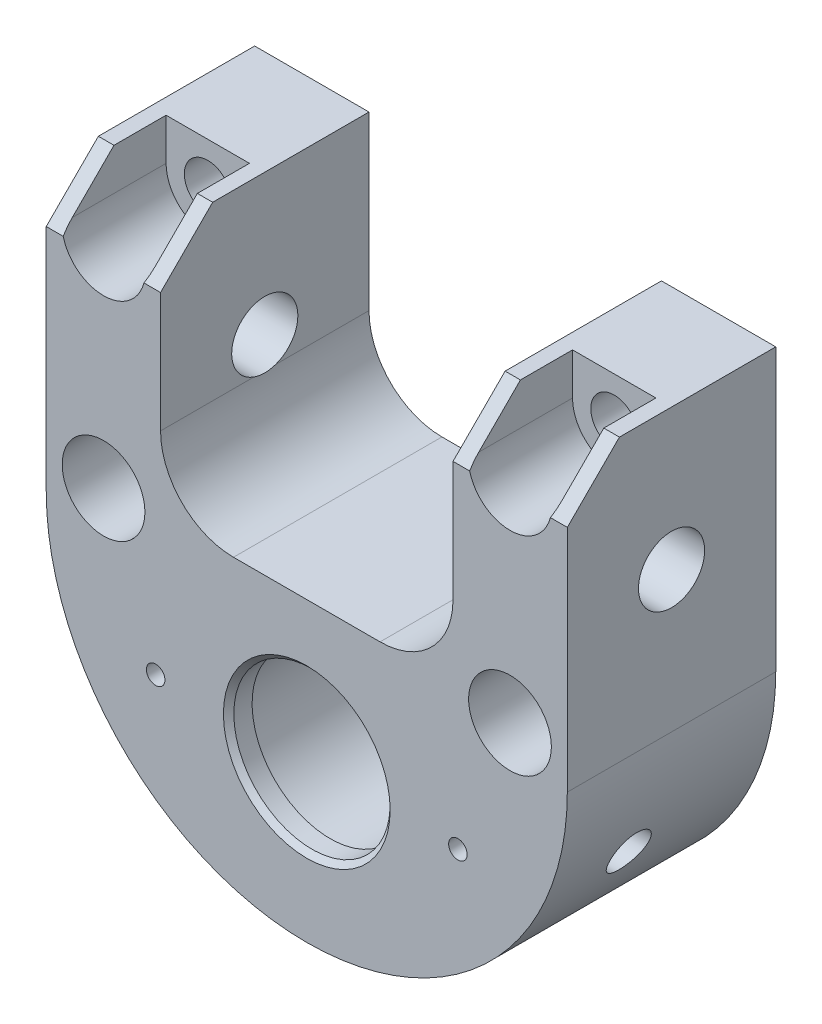
SolidWorks part; units mm, degrees
material "AISI 316 Annealed Stainless Steel Bar (SS)"
ref_plane "Front" through (0, 0, 0) normal (0, 0, 1) x (1, 0, 0)
ref_plane "Top" through (0, 0, 0) normal (0, 1, 0) x (1, 0, 0)
ref_plane "Right" through (0, 0, 0) normal (1, 0, 0) x (0, 0, -1)
sketch "Sketch1" plane through (0, 0, 0) normal (0, 0, 1) x (1, 0, 0)
  line L0 (0, 37) -> (0, 0) construction
  line L1 (-25, -15) -> (25, -15)
  line L2 (-25, -15) -> (-25, 37)
  line L3 (-25, 37) -> (25, 37)
  line L4 (25, -15) -> (25, 37)
  circle A0 centre (0, 0) radius 9.5 construction
  dimension "D3" = 19
  dimension "D5" = 15
  dimension "D1" = 52
  dimension "D2" = 50
extrude "Boss-Extrude1" add sketch "Sketch1" along normal blind 20
sketch "Sketch3" plane through (0, 0, 0) normal (1, 0, 0) x (0, 0, -1)
  line L0 (0, 0) -> (-20, 0)
  line L1 (-20, 0) -> (-20, 7.5)
  line L2 (-20, 7.5) -> (-17.75, 7.5)
  line L3 (-17.75, 7.5) -> (-17.75, 8)
  line L4 (-17.75, 8) -> (-7, 8)
  line L5 (-7, 8) -> (-7, 11)
  line L6 (-7, 11) -> (0, 11)
  line L7 (0, 37) -> (0, 0) construction
  line L8 (0, 11) -> (0, 0)
  line L9 (-20, -15) -> (-20, 37) construction
  dimension "D1" = 11
  dimension "D2" = 8
  dimension "D3" = 7.5
  dimension "D4" = 7
  dimension "D5" = 2.25
revolve "Cut-Revolve1" cut sketch "Sketch3" angle 360 about L0
hole_wizard "5/32 (0.15625) Diameter Hole1" positions "Sketch4" profile "Sketch5" hole size "5/32" standard "ANSI Inch" end condition up to next
sketch "Sketch4" plane through (25, 0, 0) normal (1, 0, 0) x (0, 0, -1)
  line L1 (0, 0) -> (-20, 0) construction
  line L2 (-20, -15) -> (-20, 37) construction
  point P0 (-12, 0)
  dimension "D1" = 8
sketch "Sketch5" plane through (25, 0, 12) normal (0, 1, 0) x (0, 0, -1)
  line L0 (0, 0) -> (0, 17)
  line L1 (0, 17) -> (1.9844, 17)
  line L2 (1.9844, 17) -> (1.9844, 0)
  line L5 (1.9844, 0) -> (0, 0)
  line L11 (0, -6.35) -> (0, 107.95) construction
  dimension "Thru Hole Dia." = 3.9688
  dimension "Thru Hole Depth" = 17
fillet "Fillet1" radius 5 1 edges at (0, 37, 20) profile chamfer
hole_wizard "#2-56 Tapped Hole1" positions "Sketch8" profile "Sketch9" tap size "#2-56" standard "ANSI Inch"
sketch "Sketch8" plane through (0, 0, 20) normal (0, 0, 1) x (1, 0, 0)
  line L0 (-14.5, 0) -> (14.5, 0)
  point P0 (-14.5, 0)
  point P2 (14.5, 0)
  dimension "D1" = 29
sketch "Sketch9" plane through (-14.5, 0, 20) normal (1, 0, 0) x (0, -1, 0)
  line L0 (0, 0) -> (0, 8.4542)
  line L1 (0, 8.4542) -> (0.889, 7.92)
  line L2 (0.889, 7.92) -> (0.889, 0)
  line L5 (0.889, 0) -> (0, 0)
  line L10 (0, 8.4542) -> (-0.889, 7.92) construction
  line L11 (0, -6.35) -> (0, 107.95) construction
  dimension "Tap Drill Dia." = 1.778
  dimension "Tap Drill Depth" = 7.92
  dimension "Drill Angle" = 118
cosmetic thread "Hole Thread1" parameters "D1"=6.2259, "D2"=2.1844
cosmetic thread "Hole Thread2" parameters "D1"=6.555, "D2"=2.1844
sketch "Sketch19" plane through (0, 0, 20) normal (0, 0, 1) x (1, 0, 0)
  line L0 (23.5, 37) -> (23.5, 33)
  line L1 (15.5, 33) -> (15.5, 37)
  line L2 (15.5, 37) -> (23.5, 37)
  line L3 (0, 0) -> (0, 32) construction
  line L4 (25, 32) -> (-25, 32) construction
  line L6 (-25, 37) -> (25, 37) construction
  line L7 (-15.5, 37) -> (-23.5, 37)
  line L8 (-15.5, 33) -> (-15.5, 37)
  line L9 (-23.5, 37) -> (-23.5, 33)
  line L10 (25, 37) -> (25, 32) construction
  arc A0 (23.5, 33) -> (15.5, 33) centre (19.5, 33) cw
  arc A1 (-23.5, 33) -> (-15.5, 33) centre (-19.5, 33) ccw
  dimension "D3" = 4
  dimension "D1" = 5.5
  dimension "D2" = 4
extrude "Cut-Extrude2" cut sketch "Sketch19" against normal blind 10
hole_wizard "#8 Clearance Hole1" positions "Sketch20" profile "Sketch21" hole size "#8" standard "ANSI Inch" end condition through all
sketch "Sketch20" plane through (0, 0, 10) normal (0, 0, 1) x (1, 0, 0)
  point P0 (19.5, 33)
  point P5 (-19.5, 33)
sketch "Sketch21" plane through (19.5, 33, 10) normal (1, 0, 0) x (0, -1, 0)
  line L0 (0, 0) -> (0, 10)
  line L1 (0, 10) -> (2.2479, 10)
  line L2 (2.2479, 10) -> (2.2479, 0)
  line L5 (2.2479, 0) -> (0, 0)
  line L11 (0, -6.35) -> (0, 107.95) construction
  dimension "Thru Hole Dia." = 4.4958
  dimension "Thru Hole Depth" = 10
hole_wizard "CBORE for #8 Socket Head Cap Screw1" positions "Sketch16" profile "Sketch17" counterbore size "#8" standard "ANSI Inch" end condition through all
sketch "Sketch16" plane through (0, 0, 20) normal (0, 0, 1) x (1, 0, 0)
  line L0 (-19.5, 13) -> (-19.5, 33) construction
  line L1 (-19.5, 33) -> (19.5, 33) construction
  line L2 (19.5, 33) -> (19.5, 13) construction
  line L5 (0, 33) -> (0, 37) construction
  line L8 (-25, 32) -> (-25, -15) construction
  line L9 (-15.5, 37) -> (15.5, 37) construction
  point P0 (-19.5, 13)
  point P6 (19.5, 13)
  dimension "D1" = 5.5
  dimension "D2" = 4
  dimension "D3" = 20
sketch "Sketch17" plane through (-19.5, 13, 20) normal (1, 0, 0) x (0, -1, 0)
  line L0 (0, 0) -> (0, 20)
  line L1 (0, 20) -> (2.2479, 20)
  line L3 (2.2479, 20) -> (2.2479, 10)
  line L4 (2.2479, 10) -> (3.9687, 10)
  line L5 (3.9687, 10) -> (3.9687, 0)
  line L7 (3.9687, 0) -> (0, 0)
  line L11 (0, -6.35) -> (0, 107.95) construction
  dimension "Thru Hole Dia." = 4.4958
  dimension "Thru Hole Depth" = 20
  dimension "C'Bore Dia." = 7.9375
  dimension "C'Bore Depth" = 10
hole_wizard "1/8 (0.1250) Dowel Hole1" positions "Sketch10" profile "Sketch11" hole size "1/8" standard "ANSI Inch"
sketch "Sketch10" plane through (0, 0, 0) normal (0, 0, -1) x (-1, 0, 0)
  line L10 (-19.5, 33) -> (-19.5, 13) construction
  point P0 (-19.5, 23)
sketch "Sketch11" plane through (19.5, 23, 0) normal (1, 0, 0) x (0, 1, 0)
  line L0 (0, 0) -> (0, 5.9539)
  line L1 (0, 5.9539) -> (1.5875, 5)
  line L2 (1.5875, 5) -> (1.5875, 0)
  line L5 (1.5875, 0) -> (0, 0)
  line L10 (0, 5.9539) -> (-1.5875, 5) construction
  line L11 (0, -6.35) -> (0, 107.95) construction
  dimension "Hole Dia." = 3.175
  dimension "Hole Depth" = 5
  dimension "Drill Angle" = 118
hole_wizard "1/8 (0.1250) Dowel Slot1" positions "Sketch12" profile "Sketch13" size "1/8" standard "ANSI Inch" slot yes
sketch "Sketch12" plane through (0, 0, 0) normal (0, 0, -1) x (-1, 0, 0)
  line L0 (17.5, 23) -> (21.5, 23) construction
  line L5 (19.5, 13) -> (19.5, 33) construction
  point P0 (19.5, 23)
  dimension "D1" = 4
sketch "Sketch13" plane through (-19.5, 23, 0) normal (1, 0, 0) x (0, 1, 0)
  line L0 (0, 0) -> (0, 5.9539)
  line L1 (0, 5.9539) -> (1.5875, 5)
  line L2 (1.5875, 5) -> (1.5875, 0)
  line L5 (1.5875, 0) -> (0, 0)
  line L10 (0, 5.9539) -> (-1.5875, 5) construction
  line L11 (0, -6.35) -> (0, 107.95) construction
  dimension "Hole Dia." = 3.175
  dimension "Hole Depth" = 5
  dimension "Drill Angle" = 118
sketch "Sketch22" plane through (0, 0, 0) normal (0, 0, -1) x (-1, 0, 0)
  circle A0 centre (0, 0) radius 10
  dimension "D1" = 20
extrude "Cut-Extrude3" [suppressed] cut sketch "Sketch22" along normal blind 1.1 from offset 2 offset against normal yes
chamfer "Chamfer1" distance 0.5 angle 45 2 edges at (0, 11, 0) (0, 7.5, 20)
sketch "Sketch23" plane through (0, 0, 20) normal (0, 0, 1) x (1, 0, 0)
  line L0 (0, 37) -> (0, 30) construction
  line L1 (-7.5313, 30) -> (7.5313, 30)
  line L2 (-13.5313, 24) -> (-13.5313, 19.5)
  line L3 (-7.5313, 13.5) -> (7.5313, 13.5)
  line L4 (13.5313, 24) -> (13.5313, 19.5)
  line L5 (-15.5, 37) -> (15.5, 37) construction
  line L6 (0, 13.5) -> (0, 11.5) construction
  line L7 (25, 37) -> (-25, 37) construction
  circle A1 centre (0, 0) radius 11.5 construction
  circle A3 centre (19.5, 13) radius 3.9688 construction
  arc A4 (-7.5313, 30) -> (-13.5313, 24) centre (-7.5313, 24) ccw
  arc A5 (-13.5313, 19.5) -> (-7.5313, 13.5) centre (-7.5313, 19.5) ccw
  arc A6 (7.5313, 13.5) -> (13.5313, 19.5) centre (7.5313, 19.5) ccw
  arc A7 (7.5313, 30) -> (13.5313, 24) centre (7.5313, 24) cw
  dimension "D2" = 2
  dimension "D3" = 6
  dimension "D1" = 7
  dimension "D4" = 2
extrude "Cut-Extrude4" [suppressed] cut sketch "Sketch23" against normal through all
fillet "Fillet2" [suppressed] radius 25
sketch "Sketch24" plane through (0, 0, 20) normal (0, 0, 1) x (1, 0, 0)
  line L0 (-15.5, 37) -> (15.5, 37) construction
  line L1 (-14.0313, 37) -> (14.0313, 37)
  line L2 (-14.0313, 37) -> (-14.0313, 20.5)
  line L3 (-7.0313, 13.5) -> (7.0313, 13.5)
  line L4 (14.0313, 37) -> (14.0313, 20.5)
  line L5 (0, 13.5) -> (0, 0) construction
  circle A0 centre (-19.5, 13) radius 3.9688 construction
  arc A1 (7.0313, 13.5) -> (14.0313, 20.5) centre (7.0313, 20.5) ccw
  arc A2 (-14.0313, 20.5) -> (-7.0313, 13.5) centre (-7.0313, 20.5) ccw
  circle A4 centre (0, 0) radius 11.5 construction
  dimension "D1" = 1.5
  dimension "D2" = 7
  dimension "D3" = 2
extrude "Cut-Extrude5" cut sketch "Sketch24" against normal through all
fillet "Fillet3" radius 25 2 edges at (25, -15, 10) (-25, -15, 10)
hole_wizard "1/4 (0.2500) Dowel Hole1" positions "Sketch25" profile "Sketch26" hole size "1/4" standard "ANSI Inch" end condition through all
sketch "Sketch25" plane through (25, 0, 0) normal (1, 0, 0) x (0, 0, -1)
  line L0 (0, 23.5) -> (-20, 23.5) construction
  line L1 (0, 10) -> (0, 37) construction
  line L2 (-20, 10) -> (-20, 32) construction
  point P0 (-10, 23.5)
sketch "Sketch26" plane through (25, 23.5, 10) normal (0, 1, 0) x (0, 0, -1)
  line L0 (0, 0) -> (0, 50)
  line L1 (0, 50) -> (3.175, 50)
  line L2 (3.175, 50) -> (3.175, 0)
  line L5 (3.175, 0) -> (0, 0)
  line L11 (0, -6.35) -> (0, 107.95) construction
  dimension "Thru Hole Dia." = 6.35
  dimension "Thru Hole Depth" = 50
